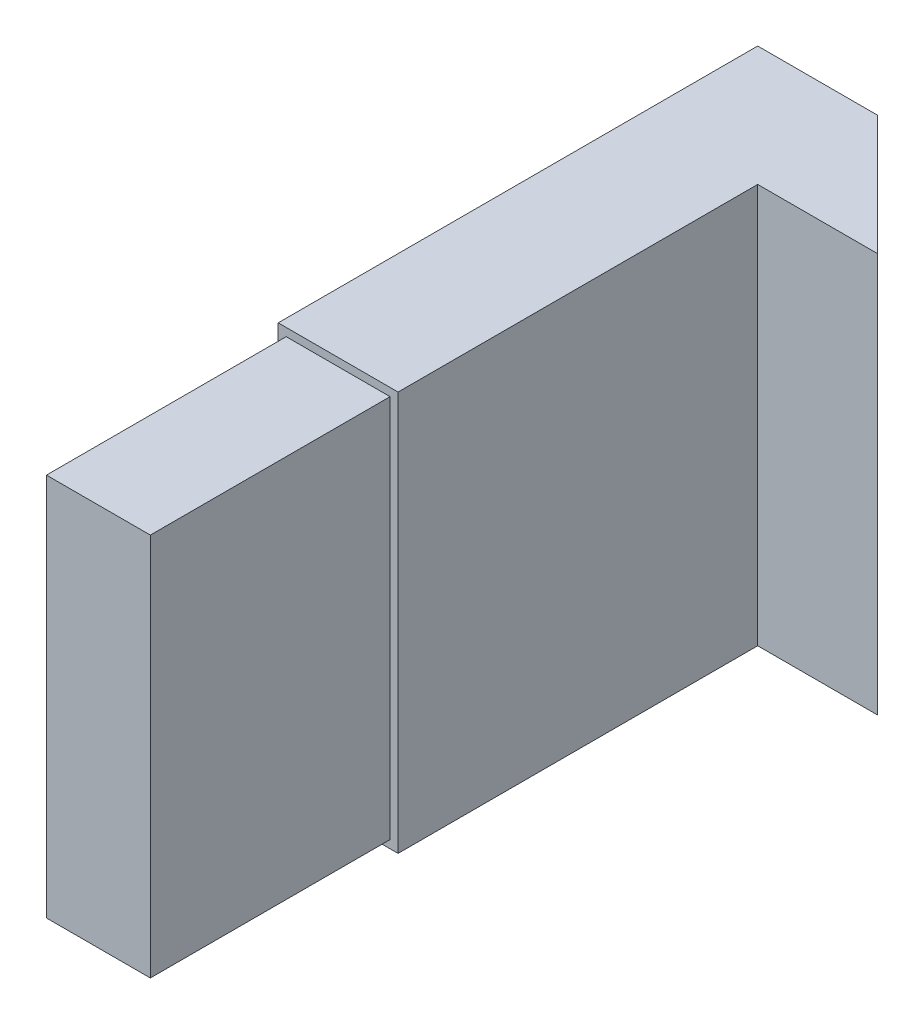
SolidWorks part; units mm, degrees
ref_plane "Front Plane" through (0, 0, 0) normal (0, 0, 1) x (1, 0, 0)
ref_plane "Top Plane" through (0, 0, 0) normal (0, 1, 0) x (1, 0, 0)
ref_plane "Right Plane" through (0, 0, 0) normal (1, 0, 0) x (0, 0, -1)
sketch "Sketch1" plane through (0, 0, 0) normal (0, 1, 0) x (1, 0, 0)
  line L0 (2.25, 1.5) -> (0.75, 3)
  line L1 (-0.75, -3) -> (0.75, -3)
  line L5 (-0.7, -3) -> (0.7, -3)
  line L7 (-0.75, 3) -> (0.75, 3)
  line L8 (-0.75, 3) -> (-0.75, -3)
  line L9 (-0.75, -3) -> (0.75, -3)
  line L10 (0.75, 1.5) -> (0.75, -3)
  line L11 (-0.75, 3) -> (0.75, -3) construction
  line L12 (-0.75, -3) -> (0.75, 3) construction
  line L13 (0.75, 1.5) -> (0.75, 3) construction
  line L15 (0.75, 1.5) -> (2.25, 1.5)
  point P6 (0, 0)
  dimension "D1" = 1.5
  dimension "D3" = 6
extrude "Boss-Extrude1" add sketch "Sketch1" along normal blind 5 contours L1 | L10 L15 L0 L7 L8 L1 region at (0.1389, 0, -0.2222)
sketch "Sketch2" plane through (0, 0, 3) normal (0, 0, 1) x (1, 0, 0)
  line L0 (-0.65, 2.5) -> (0.65, 2.5) construction
  line L1 (0, 4.9) -> (0, 0.1) construction
  line L8 (-0.65, 0.1) -> (0.65, 0.1)
  line L9 (0.65, 0.1) -> (0.65, 4.9)
  line L10 (0.65, 4.9) -> (-0.65, 4.9)
  line L11 (-0.65, 4.9) -> (-0.65, 0.1)
  line L12 (-0.65, 0.1) -> (0.65, 0.1)
  line L13 (0.65, 0.1) -> (0.65, 4.9)
  line L14 (0.65, 4.9) -> (-0.65, 4.9)
  line L15 (-0.65, 4.9) -> (-0.65, 0.1)
  dimension "D1" = 0.1
extrude "Boss-Extrude2" add sketch "Sketch2" along normal blind 3
ref_point "Point1"
ref_axis "Axis1" through (0, 2.5, -6.2512) along (0, 0, 1)
